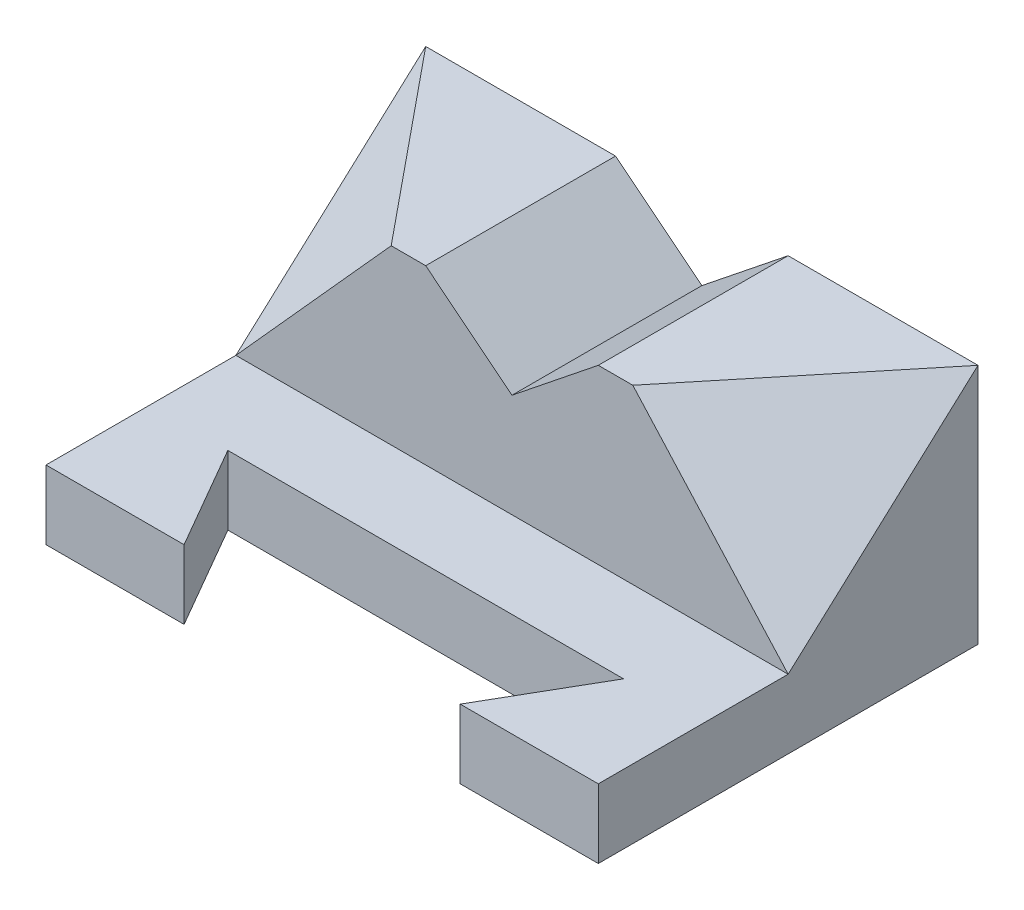
SolidWorks part; units mm, degrees
ref_plane "前视基准面" through (0, 0, 0) normal (0, 0, 1) x (1, 0, 0)
ref_plane "上视基准面" through (0, 0, 0) normal (0, 1, 0) x (1, 0, 0)
ref_plane "右视基准面" through (0, 0, 0) normal (1, 0, 0) x (0, 0, -1)
other "Configuration Table"
sketch "草图1" plane through (0, 0, 0) normal (0, 1, 0) x (1, 0, 0)
  line L1 (-32, -22) -> (32, -22)
  line L2 (-32, -22) -> (-32, 22)
  line L3 (-32, 22) -> (32, 22)
  line L4 (32, -22) -> (32, 22)
  line L5 (-32, -22) -> (32, 22) construction
  line L6 (-32, 22) -> (32, -22) construction
  point P0 (0, 0)
  dimension "D1" = 44
  dimension "D2" = 64
extrude "凸台-拉伸1" add sketch "草图1" along normal blind 8
sketch "草图2" plane through (0, 8, 0) normal (0, 1, 0) x (1, 0, 0)
  line L0 (32, -22) -> (32, 22) construction
  line L1 (-32, 22) -> (32, 22)
  line L2 (-32, 22) -> (-32, 0)
  line L3 (-32, 0) -> (32, 0)
  line L4 (32, 22) -> (32, 0)
  dimension "D1" = 22
extrude "凸台-拉伸2" add sketch "草图2" along normal blind 20
sketch "草图3" plane through (0, 8, 0) normal (0, 1, 0) x (1, 0, 0)
  line L0 (-22.9282, -10) -> (22.9282, -10)
  line L1 (-22.9282, -10) -> (-16, -22)
  line L2 (-32, -22) -> (32, -22) construction
  line L3 (0, 0) -> (0, -7.1291) construction
  line L4 (22.9282, -10) -> (16, -22)
  point P3 (0, -10)
  dimension "D1" = 16
  dimension "D2" = 12
  dimension "D3" = 60
extrude "切除-拉伸2" cut sketch "草图3" against normal through all both and the other way through all flip side to cut
sketch "草图4" plane through (0, 0, 0) normal (0, 0, 1) x (1, 0, 0)
  line L0 (0, 20) -> (10, 28)
  line L1 (-32, 28) -> (32, 28) construction
  line L2 (0, 0) -> (0, 15.1887) construction
  line L3 (0, 20) -> (-10, 28)
  dimension "D1" = 10
  dimension "D2" = 8
extrude "切除-拉伸3" cut sketch "草图4" against normal through all both and the other way through all flip side to cut
sketch3d "3D草图3"
  line L0 (32, 8, 0) -> (32, 28, -22)
  line L1 (32, 28, -22) -> (14, 28, 0)
  line L2 (10, 28, 0) -> (32, 28, 0) construction
  line L3 (14, 28, 0) -> (32, 8, 0)
  dimension "D1" = 18
extrude "切除-拉伸4" cut sketch "3D草图3" along direction (0, 0, -1) on the side of the normal through all
mirror "镜向1" about plane through (0, 0, 0) normal (1, 0, 0) of "切除-拉伸4"
